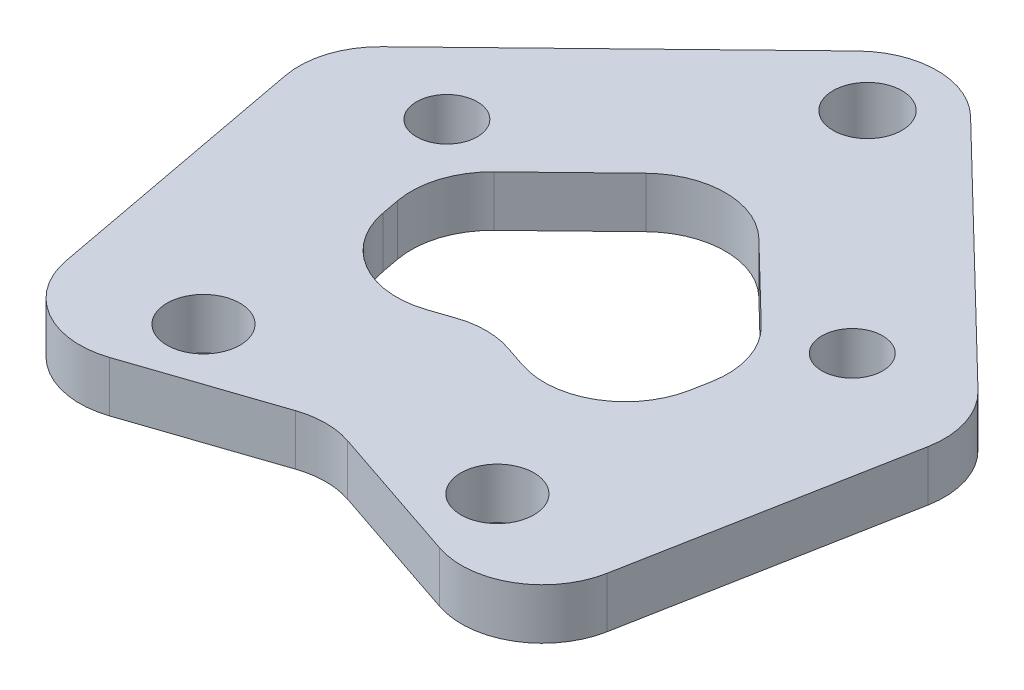
SolidWorks part; units mm, degrees
ref_plane "Front Plane" through (0, 0, 0) normal (0, 0, 1) x (1, 0, 0)
ref_plane "Top Plane" through (0, 0, 0) normal (0, 1, 0) x (1, 0, 0)
ref_plane "Right Plane" through (0, 0, 0) normal (1, 0, 0) x (0, 0, -1)
sketch "Sketch1" plane through (0, 0, 0) normal (0, 1, 0) x (1, 0, 0)
  line L0 (0, 20.0025) -> (64.77, 20.0025) construction
  line L5 (0, 38.0694) -> (0, 1.9356) construction
  line L10 (11.7475, 20.0025) -> (32.385, 40.005)
  line L11 (32.385, 40.005) -> (53.0225, 20.0025)
  line L12 (11.7475, 20.0025) -> (16.51, -5.3509)
  line L13 (64.77, 38.0694) -> (64.77, 1.9356) construction
  line L19 (48.26, -5.3509) -> (53.0225, 20.0025)
  line L22 (16.51, -5.3509) -> (32.385, 0)
  line L23 (32.385, 0) -> (48.26, -5.3509)
  point P6 (16.51, -5.4449)
  dimension "D1" = 41.275
  dimension "D2" = 31.75
  dimension "D3" = 25.7969
extrude "Boss-Extrude1" add sketch "Sketch1" along normal mid plane 3.175
sketch "Sketch2" plane through (0, -1.5875, 0) normal (0, 1, 0) x (1, 0, 0)
  line L4 (32.385, 40.005) -> (32.385, 0) construction
  line L6 (0, 40.005) -> (32.385, 40.005) construction
  circle A0 centre (19.685, 20.0025) radius 1.905
  circle A1 centre (45.085, 20.0025) radius 1.905
  circle A2 centre (19.685, 20.0025) radius 2.286 construction
  circle A3 centre (45.085, 20.0025) radius 7.239 construction
  circle A5 centre (32.385, 33.655) radius 2.159
  circle A8 centre (23.1775, 1.2597) radius 2.286
  circle A10 centre (41.5925, 1.2597) radius 2.286
  point P10 (32.385, 20.0025)
  point P23 (23.3267, 1.5594)
  point P24 (23.495, 1.6829)
  point P26 (23.3267, 2.2225)
  dimension "D1" = 3.81
  dimension "D7" = 4.318
  dimension "D4" = 9.2075
  dimension "D5" = 4.572
  dimension "D3" = 6.35
  dimension "D6" = 18.7428
extrude "Cut-Extrude1" cut sketch "Sketch2" along normal through all
sketch "Sketch4" plane through (0, 1.5875, 0) normal (0, 1, 0) x (1, 0, 0)
  line L33 (22.0543, 16.7274) -> (23.8488, 7.1743)
  line L34 (23.8488, 7.1743) -> (32.385, 10.0515)
  line L35 (32.385, 10.0515) -> (40.9212, 7.1743)
  line L36 (40.9212, 7.1743) -> (42.7157, 16.7274)
  line L37 (42.7157, 16.7274) -> (32.385, 26.7402)
  line L38 (32.385, 26.7402) -> (22.0543, 16.7274)
  line L39 (22.0543, 16.7274) -> (23.8488, 7.1743)
  line L40 (23.8488, 7.1743) -> (32.385, 10.0515)
  line L41 (32.385, 10.0515) -> (40.9212, 7.1743)
  line L42 (40.9212, 7.1743) -> (42.7157, 16.7274)
  line L43 (42.7157, 16.7274) -> (32.385, 26.7402)
  line L44 (32.385, 26.7402) -> (22.0543, 16.7274)
  dimension "D1" = 9.525
extrude "Cut-Extrude3" cut sketch "Sketch4" against normal through all
fillet "Fillet2" radius 5.08 12 edges at (23.8488, 0, -7.1743) (32.385, 0, -10.0515) (40.9212, 0, -7.1743) (42.7157, 0, -16.7274) (32.385, 0, -26.7402) (22.0543, 0, -16.7274) (11.7475, 0, -20.0025) (32.385, 0, -40.005) (53.0225, 0, -20.0025) (32.385, 0, 0) (16.51, 0, 5.3509) (48.26, 0, 5.3509)
